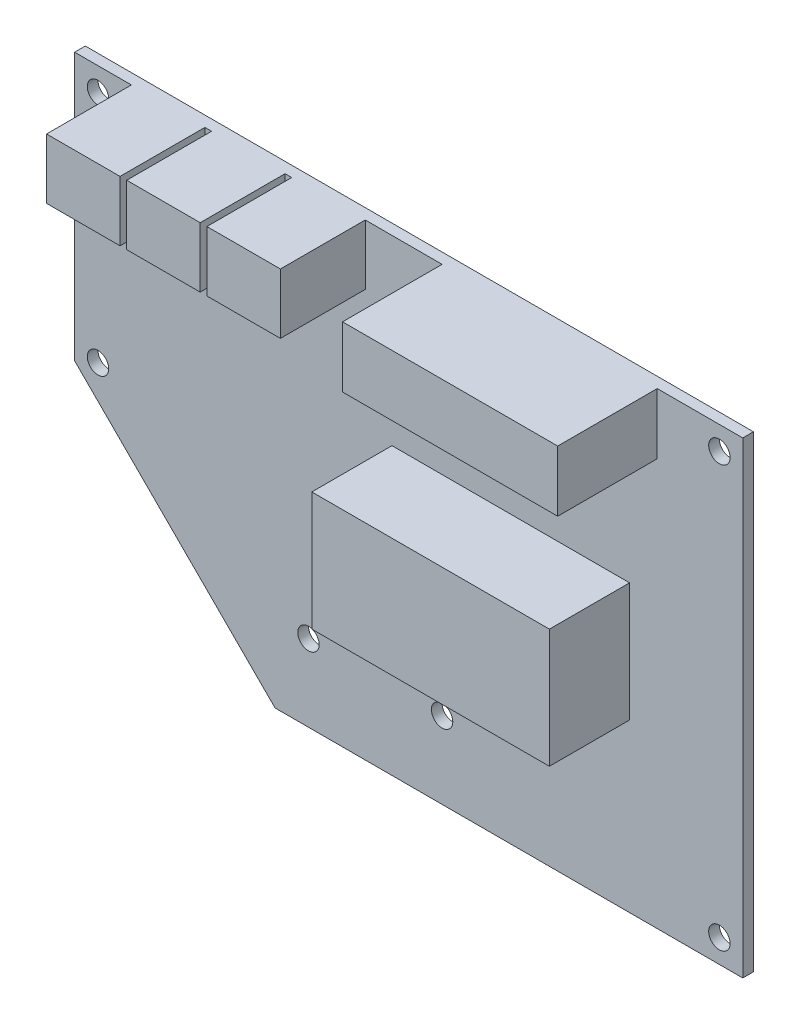
SolidWorks part; units mm, degrees
ref_plane "Plan de face" through (0, 0, 0) normal (0, 0, 1) x (1, 0, 0)
ref_plane "Plan de dessus" through (0, 0, 0) normal (0, 1, 0) x (1, 0, 0)
ref_plane "Plan de droite" through (0, 0, 0) normal (1, 0, 0) x (0, 0, -1)
sketch "Esquisse1" plane through (0, 0, 0) normal (0, 0, 1) x (1, 0, 0)
  line L0 (0, 0) -> (100, 0)
  line L1 (100, 0) -> (100, -70)
  line L2 (100, -70) -> (30, -70)
  line L3 (30, -70) -> (0, -40)
  line L4 (0, -40) -> (0, 0)
  circle A0 centre (3.5, -3.5) radius 1.6
  circle A1 centre (96.5, -3.5) radius 1.6
  circle A2 centre (3.5, -38.5) radius 1.6
  circle A3 centre (96.5, -66.5) radius 1.6
  circle A4 centre (35, -58.5) radius 1.6
  circle A5 centre (55, -58.5) radius 1.6
  point P18 (0, 0)
  point P19 (0, 0)
  dimension "D5" = 3.2
  dimension "D1" = 40
  dimension "D2" = 30
  dimension "D3" = 30
  dimension "D4" = 100
  dimension "D6" = 63
  dimension "D7" = 35
  dimension "D8" = 3.5
  dimension "D9" = 3.5
  dimension "D10" = 58.5
  dimension "D11" = 35
  dimension "D12" = 93
  dimension "D13" = 55
extrude "Boss.-Extru.1" add sketch "Esquisse1" along normal blind 1.6
sketch "Esquisse2" plane through (0, 0, 1.6) normal (0, 0, 1) x (1, 0, 0)
  line L0 (100, 0) -> (0, 0) construction
  line L1 (8.5, 0) -> (19.5, 0)
  line L2 (8.5, 0) -> (8.5, -9)
  line L3 (8.5, -9) -> (19.5, -9)
  line L4 (19.5, 0) -> (19.5, -9)
  line L15 (0, 0) -> (0, -40) construction
  line L25 (20.5, 0) -> (31.5, 0)
  line L26 (20.5, 0) -> (20.5, -9)
  line L27 (20.5, -9) -> (31.5, -9)
  line L28 (31.5, 0) -> (31.5, -9)
  line L29 (32.5, 0) -> (43.5, 0)
  line L30 (32.5, 0) -> (32.5, -9)
  line L31 (32.5, -9) -> (43.5, -9)
  line L32 (43.5, 0) -> (43.5, -9)
  dimension "D1" = 9
  dimension "D2" = 11
  dimension "D3" = 8.5
  dimension "D4" = 1
  dimension "D5" = 1
extrude "Boss.-Extru.2" add sketch "Esquisse2" along normal blind 12.7
sketch "Esquisse3" plane through (0, 0, 1.6) normal (0, 0, 1) x (1, 0, 0)
  line L5 (100, 0) -> (43.5, 0) construction
  line L6 (55, 0) -> (87.2, 0)
  line L7 (55, 0) -> (55, -9.1)
  line L8 (55, -9.1) -> (87.2, -9.1)
  line L9 (87.2, 0) -> (87.2, -9.1)
  line L10 (0, 0) -> (0, -40) construction
  dimension "D1" = 32.2
  dimension "D2" = 9.1
  dimension "D3" = 55
extrude "Boss.-Extru.3" add sketch "Esquisse3" along normal blind 14.9
sketch "Esquisse4" plane through (0, 0, 1.6) normal (0, 0, 1) x (1, 0, 0)
  line L0 (0, 0) -> (0, -40) construction
  line L1 (47.5, -27.25) -> (83.06, -27.25)
  line L2 (47.5, -27.25) -> (47.5, -45.03)
  line L3 (47.5, -45.03) -> (83.06, -45.03)
  line L4 (83.06, -27.25) -> (83.06, -45.03)
  line L5 (8.5, 0) -> (0, 0) construction
  dimension "D1" = 35.56
  dimension "D2" = 17.78
  dimension "D3" = 47.5
  dimension "D4" = 27.25
extrude "Boss.-Extru.4" add sketch "Esquisse4" along normal blind 12
